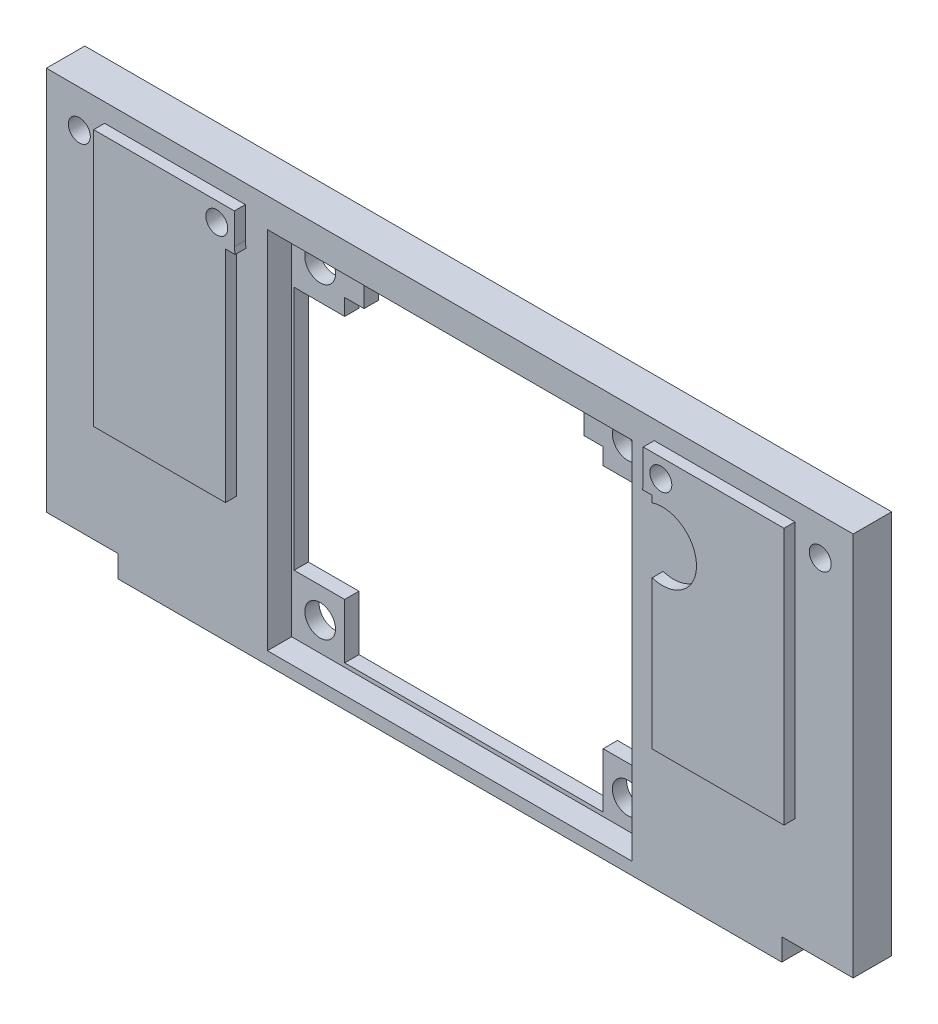
SolidWorks part; units mm, degrees
ref_plane "Front Plane" through (0, 0, 0) normal (0, 0, 1) x (1, 0, 0)
ref_plane "Top Plane" through (0, 0, 0) normal (0, 1, 0) x (1, 0, 0)
ref_plane "Right Plane" through (0, 0, 0) normal (1, 0, 0) x (0, 0, -1)
sketch "Sketch3" plane through (0, 0, 0) normal (0, 0, 1) x (1, 0, 0)
  line L0 (-39.9368, -0.9626) -> (-39.9368, 36.0374)
  line L1 (-3.2168, 30.7779) -> (-3.2168, 32.6429) construction
  line L2 (-34.7809, 21.6224) -> (-21.3928, 21.6224) construction
  line L3 (-30.5893, -0.9626) -> (18.3407, -0.9626) construction
  line L4 (-9.7818, 10.2129) -> (-9.7818, 23.3429) construction
  line L5 (-9.7818, 23.3429) -> (3.3482, 23.3429) construction
  line L6 (3.3482, 23.3429) -> (3.3482, 10.2129) construction
  line L7 (3.3482, 10.2129) -> (-9.7818, 10.2129) construction
  line L9 (-39.9368, -0.9626) -> (-14.8318, -0.9626)
  line L10 (-14.9818, 0.5374) -> (-14.9818, 5.5374)
  line L11 (-14.9818, 29.3429) -> (8.5482, 29.3429)
  line L12 (8.5482, 29.3429) -> (8.5482, 27.8429)
  line L13 (7.2982, -0.9626) -> (33.5032, -0.9626)
  line L14 (33.5032, -0.9626) -> (33.5032, 36.0374)
  line L15 (33.5032, 36.0374) -> (-39.9368, 36.0374)
  line L16 (-36.9368, 32.6429) -> (-23.4268, 32.6429) construction
  line L17 (-23.4268, 32.6429) -> (16.9932, 32.6429) construction
  line L18 (16.9932, 32.6429) -> (30.5032, 32.6429) construction
  line L19 (-17.2168, 30.7779) -> (10.7832, 30.7779) construction
  line L20 (-3.2168, 30.7779) -> (-3.2168, 23.3429) construction
  line L21 (-3.2168, 23.3429) -> (-3.2168, 10.2129) construction
  line L22 (-3.2168, 32.6429) -> (-3.2168, 42.2345) construction
  line L23 (-14.8318, -0.9626) -> (7.2982, -0.9626)
  line L24 (8.5482, 0.5374) -> (-14.9818, 0.5374)
  line L25 (-14.9818, 27.8429) -> (-19.5818, 27.8429)
  line L26 (-19.5818, 27.8429) -> (-19.5818, 5.5374)
  line L27 (-19.5818, 5.5374) -> (-14.9818, 5.5374)
  line L28 (-14.9818, 27.8429) -> (-14.9818, 29.3429)
  line L29 (8.5482, 5.5374) -> (13.1482, 5.5374)
  line L30 (13.1482, 5.5374) -> (13.1482, 27.8429)
  line L31 (13.1482, 27.8429) -> (8.5482, 27.8429)
  line L32 (8.5482, 5.5374) -> (8.5482, 0.5374)
  line L35 (-17.2168, 30.7779) -> (-17.2168, 2.7779) construction
  line L36 (-17.2168, 2.7779) -> (10.7832, 2.7779) construction
  line L37 (10.7832, 2.7779) -> (10.7832, 30.7779) construction
  circle A0 centre (-17.2168, 30.7779) radius 1.4
  circle A1 centre (-36.9368, 32.6429) radius 1
  circle A2 centre (-23.4268, 32.6429) radius 1
  circle A3 centre (16.9932, 32.6429) radius 1
  circle A4 centre (30.5032, 32.6429) radius 1
  circle A5 centre (-36.9368, 32.6429) radius 1
  circle A6 centre (-23.4268, 32.6429) radius 1
  circle A7 centre (-17.2168, 30.7779) radius 1.4
  circle A8 centre (-17.2168, 2.7779) radius 1.4
  circle A9 centre (10.7832, 30.7779) radius 1.4
  circle A10 centre (10.7832, 2.7779) radius 1.4
  point P47 (10.8482, 27.8429)
  dimension "D16" = 2
  dimension "D17" = 2.8
  dimension "D1" = 13.51
  dimension "D2" = 40.42
  dimension "D3" = 13.51
  dimension "D4" = 3.3945
  dimension "D5" = 28
  dimension "D6" = 1.865
  dimension "D7" = 13.13
  dimension "D8" = 13.13
  dimension "D9" = 7.435
  dimension "D10" = 3
  dimension "D11" = 3
  dimension "D12" = 5.2
  dimension "D13" = 5.2
  dimension "D14" = 6
  dimension "D15" = 37
  dimension "D18" = 1.5
  dimension "D19" = 5
  dimension "D20" = 9.8
  dimension "D22" = 1.5
  dimension "D23" = 9.8
  dimension "D24" = 28
extrude "Boss-Extrude1" add sketch "Sketch3" along normal blind 3.5 contours L14 L15 L0 L9 L10 L11 L12 L13 A9 A4 A3 A2 A1 A0 region at (-39.1145, 17.5374, 0)
sketch "Sketch13" plane through (0, 0, 0) normal (0, 0, -1) x (-1, 0, 0)
  line L0 (-33.5032, 36.0374) -> (39.9368, 36.0374) construction
  line L1 (-33.5032, 36.0374) -> (-16.1332, 36.0374)
  line L2 (-33.5032, 36.0374) -> (-33.5032, -0.9626)
  line L3 (-33.5032, -0.9626) -> (-16.1332, -0.9626)
  line L4 (-16.1332, 36.0374) -> (-16.1332, -0.9626)
  line L5 (39.9368, -0.9626) -> (-33.5032, -0.9626) construction
  line L7 (22.5668, 36.0374) -> (39.9368, 36.0374)
  line L8 (22.5668, 36.0374) -> (22.5668, -0.9626)
  line L9 (22.5668, -0.9626) -> (39.9368, -0.9626)
  line L10 (39.9368, 36.0374) -> (39.9368, -0.9626)
  line L11 (3.2168, 36.0374) -> (3.2168, 44.4839) construction
  line L12 (3.2168, 36.0374) -> (-16.1332, 36.0374) construction
  line L13 (3.2168, 36.0374) -> (22.5668, 36.0374) construction
  line L14 (-33.5032, -0.9626) -> (-33.5032, 36.0374) construction
  dimension "D1" = 38.7
extrude "Boss-Extrude3" [suppressed] add sketch "Sketch13" along normal blind 1
sketch "Sketch9" plane through (0, 0, 3.5) normal (0, 0, -1) x (-1, 0, 0)
  line L1 (-10.7832, 30.7779) -> (-8.9447, 28.9394) construction
  line L2 (17.2168, 2.7779) -> (17.2168, 30.7779) construction
  line L3 (17.2168, 30.7779) -> (-10.7832, 2.7779) construction
  line L4 (3.2168, 16.7779) -> (17.2168, 2.7779) construction
  line L5 (3.2168, 16.7779) -> (-10.7832, 30.7779) construction
  line L7 (-13.3832, 0.1779) -> (19.8168, 0.1779)
  line L8 (-13.3832, 0.1779) -> (-13.3832, 33.3779)
  line L9 (-13.3832, 33.3779) -> (19.8168, 33.3779)
  line L10 (19.8168, 0.1779) -> (19.8168, 33.3779)
  line L11 (-13.3832, 0.1779) -> (19.8168, 33.3779) construction
  line L12 (-13.3832, 33.3779) -> (19.8168, 0.1779) construction
  dimension "D2" = 33.2
extrude "Cut-Extrude1" cut sketch "Sketch9" along normal blind 2.2
sketch "Sketch10" plane through (0, 0, 0) normal (0, 0, -1) x (-1, 0, 0)
  line L0 (14.9818, 29.3429) -> (-8.5482, 29.3429) construction
  line L1 (-6.7832, 31.8429) -> (13.2168, 31.8429)
  line L2 (-6.7832, 31.8429) -> (-6.7832, 29.3429)
  line L3 (-6.7832, 29.3429) -> (13.2168, 29.3429)
  line L4 (13.2168, 31.8429) -> (13.2168, 29.3429)
  point P4 (3.2168, 29.3429)
  dimension "D1" = 2.5
  dimension "D2" = 20
extrude "Cut-Extrude2" cut sketch "Sketch10" against normal blind 1.75
sketch "Sketch11" plane through (0, 0, 3.5) normal (0, 0, 1) x (1, 0, 0)
  line L0 (-36.9368, 32.6429) -> (-23.4268, 32.6429) construction
  line L1 (-34.6368, 30.9429) -> (-34.6368, 10.9429)
  line L9 (-21.8268, 34.3429) -> (-34.6368, 34.3429)
  line L14 (-34.6368, 30.9429) -> (-34.6368, 34.3429)
  line L17 (-34.6368, 10.9429) -> (-22.6368, 10.9429)
  line L18 (-22.6368, 30.9429) -> (-22.6368, 10.9429)
  line L19 (-27.6818, 10.9429) -> (-27.6818, 4.0347) construction
  line L20 (-21.8268, 34.3429) -> (-21.8268, 31.5137)
  line L21 (-22.6368, 30.9429) -> (-21.7519, 30.9429)
  circle A1 centre (-36.9368, 32.6429) radius 1 construction
  circle A2 centre (-23.4268, 32.6429) radius 1
  circle A5 centre (-23.4268, 32.6429) radius 1 construction
  arc A6 (-21.8268, 31.5137) -> (-21.7519, 30.9429) centre (-18.1406, 31.707) ccw
  point P2 (-27.6818, 32.6429)
  point P16 (-34.6368, 32.6429)
  dimension "D1" = 1.6
  dimension "D2" = 12
  dimension "D3" = 2.3
  dimension "D5" = 20
extrude "Boss-Extrude2" add sketch "Sketch11" along normal blind 1
ref_plane "Plane1" through (-3.2168, 0, 0) normal (-1, 0, 0) x (0, 0, 1)
mirror "Mirror1" about plane through (-3.2168, 0, 0) normal (-1, 0, 0) of "Boss-Extrude2"
sketch "Sketch14" plane through (0, 0, 4.5) normal (0, 0, 1) x (1, 0, 0)
  circle A1 centre (17.1422, 27.3923) radius 3.1
  circle A2 centre (16.9932, 32.6429) radius 1 construction
  circle A3 centre (30.5032, 32.6429) radius 1 construction
  dimension "D1" = 6.2
  dimension "D2" = 5.2506
  dimension "D3" = 13.361
extrude "Cut-Extrude3" cut sketch "Sketch14" against normal up to surface (1 mm away) up to face at (19.2755, 26.2814, 3.5)
sketch "Sketch15" plane through (0, 0, 3.5) normal (0, 0, 1) x (1, 0, 0)
  line L1 (-39.9368, -0.9626) -> (-33.4368, -0.9626)
  line L2 (-39.9368, -0.9626) -> (-39.9368, 1.0374)
  line L3 (-39.9368, 1.0374) -> (-33.4368, 1.0374)
  line L4 (-33.4368, -0.9626) -> (-33.4368, 1.0374)
  line L5 (33.5032, -0.9626) -> (27.0032, -0.9626)
  line L6 (33.5032, -0.9626) -> (33.5032, 1.0374)
  line L7 (33.5032, 1.0374) -> (27.0032, 1.0374)
  line L8 (27.0032, -0.9626) -> (27.0032, 1.0374)
  dimension "D1" = 6.5
  dimension "D2" = 2
extrude "Cut-Extrude4" cut sketch "Sketch15" against normal through all
